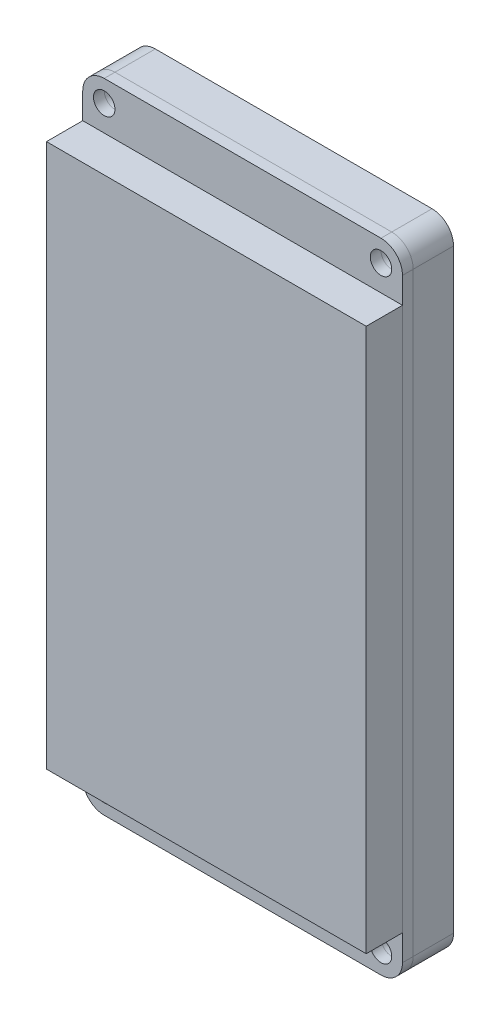
SolidWorks part; units mm, degrees
ref_plane "Front Plane" through (0, 0, 0) normal (1, 0, 0) x (0, 1, 0)
ref_plane "Top Plane" through (0, 0, 0) normal (0, 0, 1) x (0, 1, 0)
ref_plane "Right Plane" through (0, 0, 0) normal (0, 1, 0) x (-1, 0, 0)
sketch "Sketch1" plane through (0, 0, 0) normal (0, 0, 1) x (0, 1, 0)
  line L0 (-47.5, 3.8816) -> (-47.5, 45.0816)
  line L5 (-44.3, 48.2816) -> (44.3, 48.2816)
  line L6 (47.5, 45.0816) -> (47.5, 3.8816)
  line L7 (44.3, 0.6816) -> (-44.3, 0.6816)
  line L8 (0, 48.2816) -> (0, 0.6816) construction
  arc A0 (-47.5, 45.0816) -> (-44.3, 48.2816) centre (-44.3, 45.0816) cw
  arc A1 (44.3, 48.2816) -> (47.5, 45.0816) centre (44.3, 45.0816) cw
  arc A2 (47.5, 3.8816) -> (44.3, 0.6816) centre (44.3, 3.8816) cw
  arc A3 (-44.3, 0.6816) -> (-47.5, 3.8816) centre (-44.3, 3.8816) cw
  circle A4 centre (-44.3, 45.0816) radius 1.6
  circle A5 centre (-44.3, 3.8816) radius 1.6
  circle A6 centre (44.3, 3.8816) radius 1.6
  circle A7 centre (44.3, 45.0816) radius 1.6
  dimension "D1" = 95
  dimension "D3" = 3.2
  dimension "D4" = 88.6
  dimension "D2" = 47.6
extrude "Boss-Extrude1" add sketch "Sketch1" along normal blind 1.6
sketch "Sketch2" plane through (0, 0, 1.6) normal (0, 0, 1) x (1, 0, 0)
  line L0 (-48.2816, 44.3) -> (-48.2816, -44.3) construction
  line L1 (-48.2816, 40.45) -> (-0.6816, 40.45)
  line L2 (-48.2816, 40.45) -> (-48.2816, -40.45)
  line L3 (-48.2816, -40.45) -> (-0.6816, -40.45)
  line L4 (-0.6816, 40.45) -> (-0.6816, -40.45)
  line L5 (-3.8816, 47.5) -> (-45.0816, 47.5) construction
  dimension "D1" = 80.9
  dimension "D2" = 47.6
  dimension "D3" = 7.05
extrude "Boss-Extrude2" add sketch "Sketch2" along normal blind 5.4 separate body
extrude "Boss-Extrude3" add sketch "Sketch1<2>" against normal blind 6 separate body
sketch "Sketch1<2>" plane through (0, 0, 0) normal (0, 0, 1) x (0, 1, 0) same geometry as "Sketch1"
sketch "Sketch3" plane through (0, 0, 0) normal (0, 0, -1) x (1, 0, 0)
  line L0 (-3.8816, -47.5) -> (-45.0816, -47.5) construction
  line L1 (-32.0416, -47.5) -> (-16.9216, -47.5)
  line L2 (-32.0416, -47.5) -> (-32.0416, -39.7)
  line L3 (-32.0416, -39.7) -> (-16.9216, -39.7)
  line L4 (-16.9216, -47.5) -> (-16.9216, -39.7)
  line L5 (-0.6816, 44.3) -> (-0.6816, -44.3) construction
  line L6 (-48.2816, -44.3) -> (-48.2816, 44.3) construction
  dimension "D1" = 7.8
  dimension "D2" = 15.12
  dimension "D3" = 16.24
  dimension "D4" = 16.24
extrude "Boss-Extrude4" add sketch "Sketch3" along normal blind 6 separate body
equation "\"D1@Boss-Extrude2\"=4.2 + 1.2"
